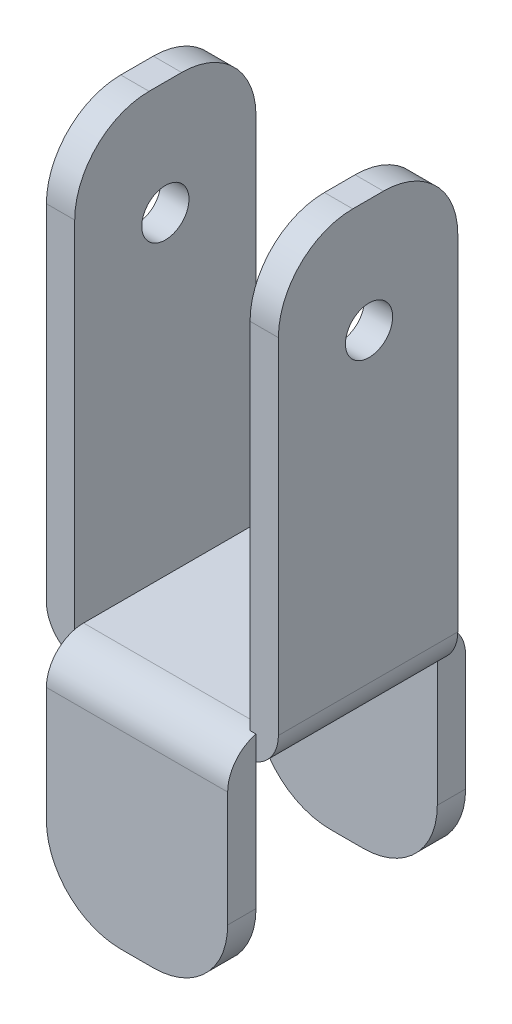
SolidWorks part; units mm, degrees
ref_plane "Front Plane" through (0, 0, 0) normal (0, 0, 1) x (1, 0, 0)
ref_plane "Top Plane" through (0, 0, 0) normal (0, 1, 0) x (1, 0, 0)
ref_plane "Right Plane" through (0, 0, 0) normal (1, 0, 0) x (0, 0, -1)
sketch "Sketch1" plane through (0, 0, 0) normal (1, 0, 0) x (0, 0, -1)
  line L1 (10, 0) -> (14.384, 0)
  line L2 (0, -10) -> (0, -57.5349)
  line L3 (0, -57.5349) -> (24.384, -57.5349)
  line L4 (24.384, -10) -> (24.384, -57.5349)
  arc A0 (14.384, 0) -> (24.384, -10) centre (14.384, -10) cw
  arc A1 (10, 0) -> (0, -10) centre (10, -10) ccw
  point P9 (0, 0)
  dimension "D1" = 10
  dimension "D2" = 24.384
extrude "Boss-Extrude1" add sketch "Sketch1" along normal blind 3.81
sketch "Sketch2" plane through (0, -57.5349, 0) normal (0, -1, 0) x (-1, 0, 0)
  line L1 (0, 24.384) -> (-27.3941, 24.384)
  line L2 (0, 24.384) -> (0, 0)
  line L3 (0, 0) -> (-27.3941, 0)
  line L4 (-27.3941, 24.384) -> (-27.3941, 0)
  dimension "D1" = 24.384
extrude "Boss-Extrude2" add sketch "Sketch2" along normal blind 3.81
sketch "Sketch7" plane through (27.3941, 0, 0) normal (1, 0, 0) x (0, 0, -1)
  line L1 (0, -61.3449) -> (24.13, -61.3449)
  line L2 (0, -61.3449) -> (0, 0)
  line L3 (0, 0) -> (24.13, 0)
  line L4 (24.13, -61.3449) -> (24.13, 0)
  dimension "D1" = 24.13
extrude "Boss-Extrude3" add sketch "Sketch7" along normal blind 3.81
fillet "Fillet1" radius 10 1 edges at (29.2991, 0, -24.13)
fillet "Fillet2" radius 10 1 edges at (29.2991, 0, 0)
fillet "Fillet3" radius 5 1 edges at (31.2041, -61.3449, -12.065)
fillet "Fillet4" radius 5 1 edges at (0, -61.3449, -12.192)
sketch "Sketch8" plane through (0, 0, -24.384) normal (0, 0, -1) x (-1, 0, 0)
  line L0 (-3.81, -57.5349) -> (-3.81, -10) construction
  line L1 (-3.81, -57.693) -> (-28.194, -57.693)
  line L2 (-3.81, -57.693) -> (-3.81, -88.173)
  line L3 (-3.81, -88.173) -> (-28.194, -88.173)
  line L4 (-28.194, -57.693) -> (-28.194, -88.173)
  dimension "D1" = 24.384
  dimension "D2" = 30.48
extrude "Boss-Extrude4" add sketch "Sketch8" along normal blind 3.81 contours L2 L3 L4 L1
fillet "Fillet5" radius 5 1 edges at (16.002, -57.693, -28.194)
fillet "Fillet6" radius 10 1 edges at (3.81, -88.173, -26.289)
fillet "Fillet8" radius 10 1 edges at (28.194, -88.173, -26.289)
sketch "Sketch9" plane through (0, 0, 0) normal (0, 0, 1) x (1, 0, 0)
  line L1 (3.81, -57.5349) -> (28.194, -57.5349)
  line L2 (3.81, -57.5349) -> (3.81, -88.0149)
  line L3 (3.81, -88.0149) -> (28.194, -88.0149)
  line L4 (28.194, -57.5349) -> (28.194, -88.0149)
  dimension "D1" = 30.48
  dimension "D2" = 24.384
extrude "Boss-Extrude5" add sketch "Sketch9" along normal blind 3.81
fillet "Fillet9" radius 10 1 edges at (3.81, -88.0149, 1.905)
fillet "Fillet10" radius 10 1 edges at (28.194, -88.0149, 1.905)
fillet "Fillet11" radius 5 1 edges at (16.002, -57.5349, 3.81)
hole_wizard "1/4 (0.25) Diameter Hole1" positions "3DSketch1" profile "Sketch11" hole size "1/4" standard "ANSI Inch" end condition through all
sketch3d "3DSketch1"
  line L0 (0, -10, 0) -> (0, -56.3449, 0) construction
  line L1 (0, 0, -14.384) -> (0, 0, -10) construction
  point P0 (0, -15.24, -12.192)
  dimension "D1" = 12.192
  dimension "D2" = 15.24
sketch "Sketch11" plane through (0, -15.24, -12.192) normal (0, 1, 0) x (0, 0, 1)
  line L0 (0, 0) -> (0, 31.2041)
  line L1 (0, 31.2041) -> (3.175, 31.2041)
  line L2 (3.175, 31.2041) -> (3.175, 0)
  line L5 (3.175, 0) -> (0, 0)
  line L11 (0, -6.35) -> (0, 107.95) construction
  dimension "Thru Hole Dia." = 6.35
  dimension "Thru Hole Depth" = 31.2041
